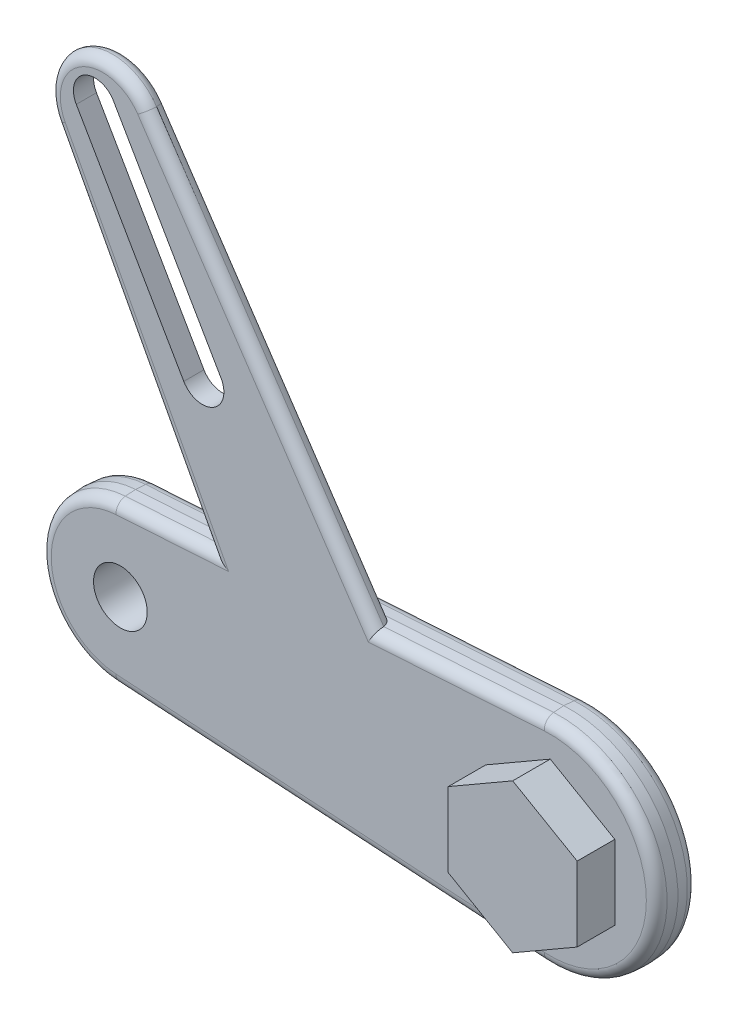
SolidWorks part; units mm, degrees
ref_plane "Спереди" through (0, 0, 0) normal (0, 0, 1) x (1, 0, 0)
ref_plane "Сверху" through (0, 0, 0) normal (0, 1, 0) x (1, 0, 0)
ref_plane "Справа" through (0, 0, 0) normal (1, 0, 0) x (0, 0, -1)
sketch "Эскиз1" plane through (0, 0, 0) normal (0, 0, 1) x (1, 0, 0)
  line L0 (-32.8446, 0) -> (47.1554, 0) construction
  line L1 (-33.7821, 14.9707) -> (45.9054, 19.9609)
  line L2 (-33.7821, -14.9707) -> (45.9054, -19.9609)
  arc A0 (-33.7821, 14.9707) -> (-33.7821, -14.9707) centre (-32.8446, 0) ccw
  arc A1 (45.9054, -19.9609) -> (45.9054, 19.9609) centre (47.1554, 0) ccw
  dimension "D2" = 30
  dimension "D3" = 40
  dimension "D1" = 80
  dimension "D4" = 45.9054
extrude "Основание" add sketch "Эскиз1" along normal mid plane 7.5 draft 4
sketch "Эскиз2" plane through (0, 0, 0) normal (0, 0, 1) x (1, 0, 0)
  line L0 (7.1554, 0) -> (-36.1458, 75) construction
  line L1 (-44.9753, 70.3053) -> (-7.5933, 0)
  line L2 (-32.8446, 0) -> (47.1554, 0) construction
  line L3 (-27.8555, 80.5919) -> (26.3916, 0.1673)
  line L4 (-7.5933, 0) -> (26.3916, 0.1673)
  arc A0 (-27.8555, 80.5919) -> (-44.9753, 70.3053) centre (-36.1458, 75) ccw
  point P10 (-50.1861, 80.1054)
  dimension "D5" = 20
  dimension "D1" = 120
  dimension "D2" = 75
  dimension "D3" = 4
  dimension "D4" = 2
  dimension "D6" = 26.3916
extrude "Ручка с прорезью" add sketch "Эскиз2" along normal through all draft 4
sketch "Эскиз3" plane through (0, 0, 3.75) normal (0, 0, 1) x (1, 0, 0)
  line L0 (-37.5834, 77.2693) -> (-17.5834, 42.6283) construction
  line L1 (-34.1193, 79.2693) -> (-14.1193, 44.6283)
  line L2 (-41.0475, 75.2693) -> (-21.0475, 40.6283)
  line L3 (-30.6908, 0) -> (45.6162, 0) construction
  arc A0 (-34.1193, 79.2693) -> (-41.0475, 75.2693) centre (-37.5834, 77.2693) ccw
  arc A1 (-21.0475, 40.6283) -> (-14.1193, 44.6283) centre (-17.5834, 42.6283) ccw
  point P2 (-27.5834, 59.9488)
  dimension "D3" = 4
  dimension "D1" = 120
  dimension "D2" = 40
  dimension "D4" = 3.6963
  dimension "D5" = 1.176
extrude "Вырез-Вытянуть1" cut sketch "Эскиз3" against normal through all
sketch "Эскиз4" plane through (0, 0, 3.75) normal (0, 0, 1) x (1, 0, 0)
  circle A0 centre (-32.8446, 0) radius 5
  dimension "D1" = 10
extrude "Вырез-Вытянуть2" cut sketch "Эскиз4" against normal through all
sketch "Эскиз6" plane through (0, 0, 3.75) normal (0, 0, 1) x (1, 0, 0)
  line L1 (47.1554, 13.8564) -> (35.1554, 6.9282)
  line L2 (35.1554, 6.9282) -> (35.1554, -6.9282)
  line L3 (35.1554, -6.9282) -> (47.1554, -13.8564)
  line L4 (47.1554, -13.8564) -> (59.1554, -6.9282)
  line L5 (59.1554, -6.9282) -> (59.1554, 6.9282)
  line L6 (59.1554, 6.9282) -> (47.1554, 13.8564)
  circle A0 centre (47.1554, 0) radius 12 construction
  dimension "D1" = 24
extrude "Бобышка-Вытянуть4" add sketch "Эскиз6" along normal blind 7
fillet "Скругление1" radius 2 12 edges at (-47.5823, 0, -3.75) (66.8932, 0, 3.75) (30.0805, 18.7072, 3.75) (-47.5823, 0, 3.75) (6.0781, -17.2041, 3.75) (6.0781, -17.2041, -3.75) (-24.7419, 15.2741, 3.75) (-6.9169, 49.0802, 3.75) (-41.1612, 83.3469, 3.75) (-30.231, 43.1338, 3.75) (66.8932, 0, -3.75) (6.0781, 17.2041, -3.75)
fillet "Скругление2" radius 2 3 edges at (-30.5581, 43.1903, 0) (-41.2962, 83.5717, 0) (-6.7414, 49.2891, 0)
